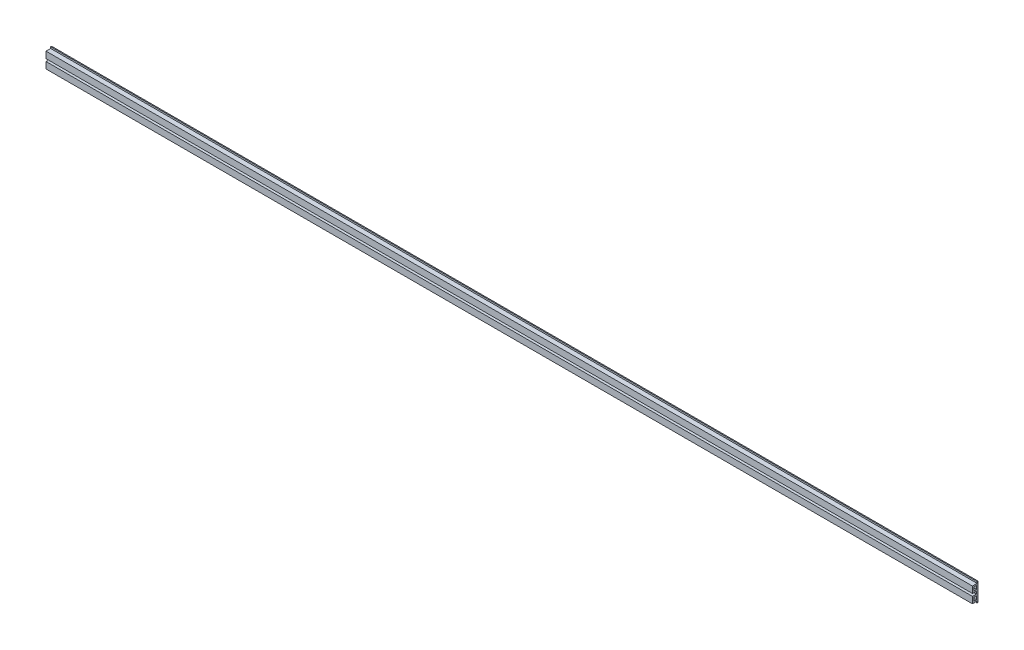
SolidWorks part; units mm, degrees
ref_plane "Спереди" through (0, 0, 0) normal (0, 0, 1) x (1, 0, 0)
ref_plane "Сверху" through (0, 0, 0) normal (0, 1, 0) x (1, 0, 0)
ref_plane "Справа" through (0, 0, 0) normal (1, 0, 0) x (0, 0, -1)
sketch "Эскиз1" plane through (0, 0, 0) normal (1, 0, 0) x (0, 0, -1)
  line L0 (0, -30) -> (0, 30)
  line L1 (0, 30) -> (-3, 30)
  line L2 (-3, 30) -> (-3, 25)
  line L3 (-3, 25) -> (-18, 25)
  line L4 (-18, 25) -> (-18, 4)
  line L5 (-18, 4) -> (-5, 4)
  line L6 (-5, 4) -> (-5, -4)
  line L7 (-5, -4) -> (-18, -4)
  line L8 (-18, -4) -> (-18, -25)
  line L9 (-18, -25) -> (-3, -25)
  line L10 (-3, -25) -> (-3, -30)
  line L11 (-3, -30) -> (0, -30)
  line L12 (0, 0) -> (-42.5697, 0) construction
  line L13 (-5, 20) -> (-13, 20)
  line L14 (-13, 20) -> (-13, 9)
  line L15 (-13, 9) -> (-5, 9)
  line L16 (-5, -9) -> (-13, -9)
  line L17 (-13, -9) -> (-13, -20)
  line L18 (-13, -20) -> (-5, -20)
  line L19 (-5, 9) -> (-5, 20)
  line L20 (-5, -9) -> (-5, -20)
  line L22 (-13, -20) -> (-3, -20) construction
  line L23 (-3, 20) -> (-13, 20) construction
  point P16 (0, 0)
  dimension "D1" = 60
  dimension "D2" = 5
  dimension "D3" = 8
  dimension "D4" = 3
  dimension "D5" = 5
  dimension "D6" = 18
  dimension "D7" = 5
extrude "Бобышка-Вытянуть1" add sketch "Эскиз1" against normal up to surface (3000 mm away)
